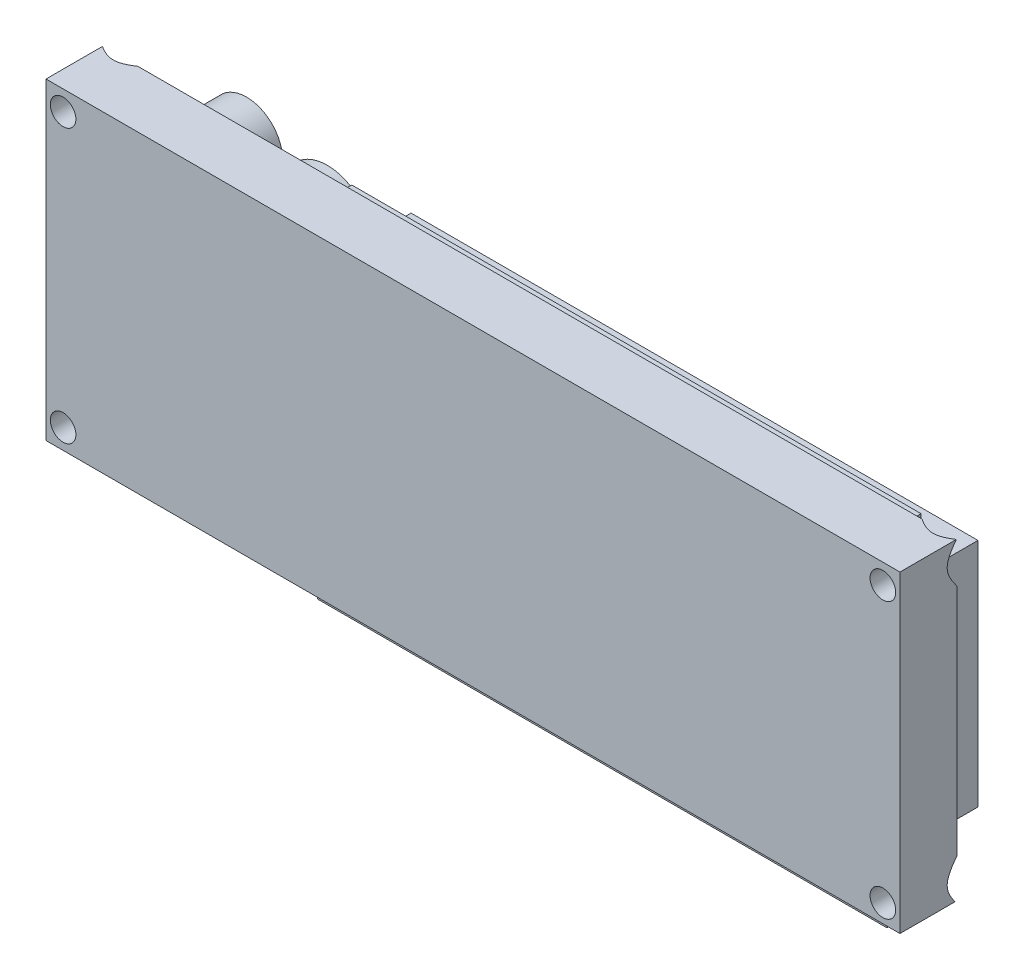
SolidWorks part; units mm, degrees
ref_plane "Front Plane" through (0, 0, 0) normal (0, 0, 1) x (1, 0, 0)
ref_plane "Top Plane" through (0, 0, 0) normal (0, 1, 0) x (1, 0, 0)
ref_plane "Right Plane" through (0, 0, 0) normal (1, 0, 0) x (0, 0, -1)
sketch "Sketch1" plane through (0, 0, 0) normal (0, 0, 1) x (1, 0, 0)
  line L1 (75, -27.5) -> (-75, -27.5)
  line L2 (75, -27.5) -> (75, 27.5)
  line L3 (75, 27.5) -> (-75, 27.5)
  line L4 (-75, -27.5) -> (-75, 27.5)
  line L5 (75, -27.5) -> (-75, 27.5) construction
  line L6 (75, 27.5) -> (-75, -27.5) construction
  point P0 (0, 0)
extrude "Boss-Extrude1" add sketch "Sketch1" along normal blind 10
hole_wizard "CSK for M4 Countersunk Flat Head Screw1" positions "Sketch2" profile "Sketch3" countersink size "M4" standard "ISO" end condition through all
sketch "Sketch2" plane through (0, 0, 0) normal (0, 0, -1) x (-1, 0, 0)
  point P0 (-72, 24)
  point P2 (-72, -24.3198)
  point P4 (72, -24)
  point P6 (72, 24)
  point P7 (0, 0)
  point P8 (0, 0)
sketch "Sketch3" plane through (72, 24, 0) normal (1, 0, 0) x (0, 1, 0)
  line L0 (0, 0) -> (0, 10)
  line L1 (0, 10) -> (2.25, 10)
  line L2 (2.25, 10) -> (2.25, 2.45)
  line L3 (2.25, 2.45) -> (4.7, 0)
  line L5 (4.7, 0) -> (0, 0)
  line L6 (-2.25, 2.45) -> (-4.7, 0) construction
  line L11 (0, -6.35) -> (0, 107.95) construction
  dimension "Thru Hole Dia." = 4.5
  dimension "Thru Hole Depth" = 10
  dimension "Near C'Sink Dia." = 9.4
  dimension "Near C'Sink Angle" = 90
sketch "Sketch4" plane through (0, 0, 0) normal (0, 0, -1) x (-1, 0, 0)
  line L1 (37.29, -37.7679) -> (-62.71, -37.7679)
  line L2 (37.29, -37.7679) -> (37.29, 22.2321)
  line L3 (37.29, 22.2321) -> (-62.71, 22.2321)
  line L4 (-62.71, -37.7679) -> (-62.71, 22.2321)
  line L5 (37.29, -37.7679) -> (-62.71, 22.2321) construction
  line L6 (37.29, 22.2321) -> (-62.71, -37.7679) construction
  point P0 (-12.71, -7.7679)
  point P5 (-12.71, -7.7679)
extrude "Boss-Extrude2" add sketch "Sketch4" along normal blind 6
sketch "Sketch5" plane through (0, 0, -6) normal (0, 0, -1) x (-1, 0, 0)
  line L0 (-62.71, 22.2321) -> (-62.71, -37.7679) construction
  line L1 (36.8772, 13.1652) -> (-62.71, 13.1652)
  line L2 (36.8772, 13.1652) -> (36.8772, -27.3892)
  line L3 (36.8772, -27.3892) -> (-62.71, -27.3892)
  line L4 (-62.71, 13.1652) -> (-62.71, -27.3892)
  line L5 (36.8772, 13.1652) -> (-62.71, -27.3892) construction
  line L6 (36.8772, -27.3892) -> (-62.71, 13.1652) construction
  point P0 (-12.9164, -7.112)
  point P7 (-12.9164, -7.112)
extrude "Boss-Extrude3" add sketch "Sketch5" along normal blind 10
sketch "Sketch6" plane through (0, 0, 0) normal (0, 0, -1) x (-1, 0, 0)
  circle A0 centre (59.7716, 16.0414) radius 6.3254
extrude "Boss-Extrude4" add sketch "Sketch6" along normal blind 10
sketch "Sketch7" plane through (0, 0, 0) normal (0, 0, -1) x (-1, 0, 0)
  line L1 (57.7679, -16.3134) -> (63.3813, -16.3134)
  line L2 (57.7679, -16.3134) -> (57.7679, -22.2536)
  line L3 (57.7679, -22.2536) -> (63.3813, -22.2536)
  line L4 (63.3813, -16.3134) -> (63.3813, -22.2536)
  line L5 (57.7679, -16.3134) -> (63.3813, -22.2536) construction
  line L6 (57.7679, -22.2536) -> (63.3813, -16.3134) construction
  circle A0 centre (60.5746, -3.7361) radius 6.761
  point P0 (60.5746, -19.2835)
extrude "Boss-Extrude5" add sketch "Sketch7" along normal blind 5
sketch "Sketch8" plane through (0, 0, -5) normal (0, 0, -1) x (-1, 0, 0)
  circle A0 centre (60.5746, -3.7361) radius 7.8253
extrude "Boss-Extrude6" add sketch "Sketch8" along normal blind 20
